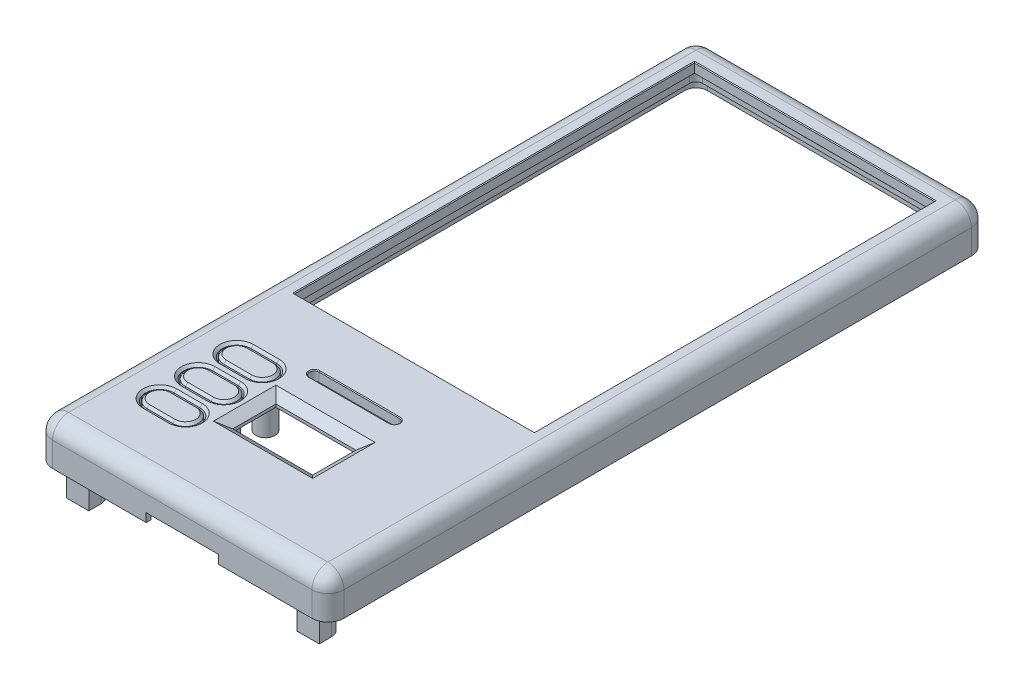
SolidWorks part; units mm, degrees
material "ABS"
ref_plane "Front Plane" through (0, 0, 0) normal (0, 0, 1) x (1, 0, 0)
ref_plane "Top Plane" through (0, 0, 0) normal (0, 1, 0) x (1, 0, 0)
ref_plane "Right Plane" through (0, 0, 0) normal (1, 0, 0) x (0, 0, -1)
sketch "Sketch1" plane through (0, 0, 0) normal (0, 1, 0) x (1, 0, 0)
  line L1 (-45.5, -103) -> (45.5, -103)
  line L2 (-45.5, -103) -> (-45.5, 103)
  line L3 (-45.5, 103) -> (45.5, 103)
  line L4 (45.5, -103) -> (45.5, 103)
  line L5 (-45.5, -103) -> (45.5, 103) construction
  line L6 (-45.5, 103) -> (45.5, -103) construction
  point P0 (0, 0)
  dimension "D1" = 91
  dimension "D2" = 206
extrude "Boss-Extrude1" add sketch "Sketch1" along normal blind 3
fillet "Fillet1" radius 5 4 edges at (45.5, 1.5, -103) (-45.5, 1.5, -103) (-45.5, 1.5, 103) (45.5, 1.5, 103)
sketch "Sketch2" plane through (0, 0, 0) normal (0, -1, 0) x (1, 0, 0)
  line L28 (-40.5, 103) -> (40.5, 103) construction
  line L29 (-40.5, -103) -> (40.5, -103)
  line L30 (-45.5, -98) -> (-45.5, 98)
  line L31 (-40.5, 103) -> (40.5, 103)
  line L32 (45.5, -98) -> (45.5, 98)
  line L33 (-45.5, -103) -> (45.5, 103) construction
  line L34 (-45.5, 103) -> (45.5, -103) construction
  line L35 (45.5, 98) -> (45.5, -98) construction
  line L36 (-42.5, -98) -> (-42.5, 98)
  line L37 (-40.5, 100) -> (40.5, 100)
  line L38 (42.5, -98) -> (42.5, 98)
  line L39 (-40.5, -100) -> (40.5, -100)
  arc A28 (40.5, -103) -> (45.5, -98) centre (40.5, -98) ccw
  arc A29 (-40.5, -103) -> (-45.5, -98) centre (-40.5, -98) cw
  arc A30 (40.5, 103) -> (45.5, 98) centre (40.5, 98) cw
  arc A31 (-45.5, 98) -> (-40.5, 103) centre (-40.5, 98) cw
  arc A32 (-42.5, 98) -> (-40.5, 100) centre (-40.5, 98) cw
  arc A33 (40.5, 100) -> (42.5, 98) centre (40.5, 98) cw
  arc A34 (40.5, -100) -> (42.5, -98) centre (40.5, -98) ccw
  arc A35 (-40.5, -100) -> (-42.5, -98) centre (-40.5, -98) cw
  point P0 (0, 0)
  dimension "D1" = 5
  dimension "D2" = 3
extrude "Boss-Extrude2" add sketch "Sketch2" along normal blind 7
sketch "Sketch3" plane through (0, 0, 0) normal (0, -1, 0) x (1, 0, 0)
  line L0 (40.5, 100) -> (-40.5, 100) construction
  line L1 (-37.5, 30.5) -> (37.5, 30.5)
  line L2 (-37.5, 30.5) -> (-37.5, -94.5)
  line L3 (-37.5, -94.5) -> (37.5, -94.5)
  line L4 (37.5, 30.5) -> (37.5, -94.5)
  line L5 (-37.5, 30.5) -> (37.5, -94.5) construction
  line L6 (-37.5, -94.5) -> (37.5, 30.5) construction
  line L7 (12.5, 49.25) -> (-12.5, 49.25) construction
  line L8 (-12.5, 61.25) -> (12.5, 61.25)
  line L9 (-12.5, 61.25) -> (-12.5, 74.75)
  line L10 (-12.5, 74.75) -> (12.5, 74.75)
  line L11 (12.5, 61.25) -> (12.5, 74.75)
  line L12 (-12.5, 61.25) -> (12.5, 74.75) construction
  line L13 (-12.5, 74.75) -> (12.5, 61.25) construction
  line L14 (12.5, 47.75) -> (-12.5, 47.75)
  line L15 (12.5, 50.75) -> (-12.5, 50.75)
  line L16 (-40.5, -103) -> (40.5, -103) construction
  line L17 (-40.5, 103) -> (40.5, 103) construction
  arc A0 (12.5, 47.75) -> (12.5, 50.75) centre (12.5, 49.25) ccw
  arc A1 (-12.5, 50.75) -> (-12.5, 47.75) centre (-12.5, 49.25) ccw
  point P0 (0, -32)
  point P9 (0, 68)
  point P17 (0, 49.25)
  point P25 (0, 103)
  dimension "D1" = 75
  dimension "D2" = 125
  dimension "D3" = 71
  dimension "D4" = 25
  dimension "D5" = 13.5
  dimension "D6" = 32
  dimension "D7" = 25
  dimension "D8" = 12
  dimension "D9" = 3
extrude "Cut-Extrude1" cut sketch "Sketch3" against normal up to next
sketch "Sketch4" plane through (0, 0, 0) normal (0, -1, 0) x (1, 0, 0)
  line L0 (-21, 80) -> (-21, 56) construction
  line L1 (-12.5, 74.75) -> (-12.5, 61.25) construction
  line L6 (12.5, 74.75) -> (-12.5, 74.75) construction
  circle A0 centre (-21, 80) radius 3
  circle A1 centre (-21, 56) radius 3
  circle A2 centre (-21, 68) radius 3
  point P11 (-12.5, 68)
  point P12 (0, 74.75)
  dimension "D4" = 6
  dimension "D5" = 6
  dimension "D6" = 6
  dimension "D1" = 21
  dimension "D3" = 24
extrude "Boss-Extrude3" add sketch "Sketch4" along normal blind 13
sketch "Sketch5" plane through (0, 0, 0) normal (0, -1, 0) x (1, 0, 0)
  line L2 (-22, 56) -> (-30, 56) construction
  line L3 (-22, 52) -> (-30, 52)
  line L4 (-22, 60) -> (-30, 60)
  line L5 (-21, 59) -> (-21, 53) construction
  line L7 (-22, 51.5) -> (-30, 51.5)
  line L8 (-22, 60.5) -> (-30, 60.5)
  line L9 (-22, 63.5) -> (-30, 63.5)
  line L10 (-22, 72.5) -> (-30, 72.5)
  line L11 (-22, 68) -> (-30, 68) construction
  line L12 (-22, 64) -> (-30, 64)
  line L13 (-22, 72) -> (-30, 72)
  line L14 (-22, 75.5) -> (-30, 75.5)
  line L15 (-22, 84.5) -> (-30, 84.5)
  line L16 (-22, 80) -> (-30, 80) construction
  line L17 (-22, 76) -> (-30, 76)
  line L18 (-22, 84) -> (-30, 84)
  line L19 (-22, 51.5) -> (-22, 63.5) construction
  arc A0 (-22, 52) -> (-22, 60) centre (-22, 56) ccw
  arc A1 (-30, 60) -> (-30, 52) centre (-30, 56) ccw
  circle A11 centre (-21, 56) radius 3 construction
  arc A12 (-30, 60.5) -> (-30, 51.5) centre (-30, 56) ccw
  arc A13 (-22, 51.5) -> (-22, 60.5) centre (-22, 56) ccw
  arc A14 (-30, 72.5) -> (-30, 63.5) centre (-30, 68) ccw
  arc A15 (-22, 63.5) -> (-22, 72.5) centre (-22, 68) ccw
  arc A16 (-22, 64) -> (-22, 72) centre (-22, 68) ccw
  arc A17 (-30, 72) -> (-30, 64) centre (-30, 68) ccw
  arc A18 (-30, 84.5) -> (-30, 75.5) centre (-30, 80) ccw
  arc A19 (-22, 75.5) -> (-22, 84.5) centre (-22, 80) ccw
  arc A20 (-22, 76) -> (-22, 84) centre (-22, 80) ccw
  arc A21 (-30, 84) -> (-30, 76) centre (-30, 80) ccw
  point P2 (-26, 56)
  point P10 (-21, 56)
  point P21 (-26, 68)
  point P34 (-26, 80)
  dimension "D1" = 8
  dimension "D5" = 12
  dimension "D3" = 0.5
  dimension "D4" = 3
  dimension "D2" = 8
extrude "Cut-Extrude4" cut sketch "Sketch5" against normal up to next
sketch "Sketch18" plane through (0, 0, 0) normal (0, -1, 0) x (1, 0, 0)
  line L0 (-33.7081, 66.5) -> (-34.5, 66.5)
  line L1 (-33.7081, 54.5) -> (-34.5, 54.5)
  line L2 (-33.7081, 54.5) -> (-33.7081, 57.5)
  line L3 (-33.7081, 57.5) -> (-34.5, 57.5)
  line L4 (-34.5, 54.5) -> (-34.5, 57.5)
  line L5 (-33.7081, 66.5) -> (-33.7081, 69.5)
  line L6 (-33.7081, 69.5) -> (-34.5, 69.5)
  line L7 (-34.5, 66.5) -> (-34.5, 69.5)
  line L8 (-33.7081, 78.5) -> (-34.5, 78.5)
  line L9 (-33.7081, 78.5) -> (-33.7081, 81.5)
  line L10 (-33.7081, 81.5) -> (-34.5, 81.5)
  line L11 (-34.5, 78.5) -> (-34.5, 81.5)
  line L12 (-33.7081, 54.5) -> (-33.7081, 66.5) construction
  arc A0 (-30, 60) -> (-30, 52) centre (-30, 56) ccw construction
  arc A1 (-30, 60.5) -> (-30, 51.5) centre (-30, 56) ccw construction
  point P13 (-34, 56)
  point P14 (-33.7081, 56)
  dimension "D1" = 3
  dimension "D3" = 12
  dimension "D2" = 3
extrude "Boss-Extrude8" add sketch "Sketch18" against normal blind 2
sketch "Sketch8" plane through (0, -7, 0) normal (0, -1, 0) x (1, 0, 0)
  line L12 (40.5, 103) -> (-40.5, 103) construction
  line L13 (45.5, -98) -> (45.5, 98) construction
  line L14 (-45.5, 98) -> (-45.5, -98) construction
  line L15 (-40.5, -103) -> (40.5, -103) construction
  line L16 (40.5, 103) -> (-40.5, 103)
  line L17 (45.5, -98) -> (45.5, 98)
  line L18 (-45.5, 98) -> (-45.5, -98)
  line L19 (-40.5, -103) -> (40.5, -103)
  line L20 (40.5, 101.5) -> (-40.5, 101.5)
  line L21 (-44, 98) -> (-44, -98)
  line L22 (-40.5, -101.5) -> (40.5, -101.5)
  line L23 (44, -98) -> (44, 98)
  arc A12 (45.5, 98) -> (40.5, 103) centre (40.5, 98) ccw construction
  arc A13 (-40.5, 103) -> (-45.5, 98) centre (-40.5, 98) ccw construction
  arc A14 (40.5, -103) -> (45.5, -98) centre (40.5, -98) ccw construction
  arc A15 (-45.5, -98) -> (-40.5, -103) centre (-40.5, -98) ccw construction
  arc A16 (45.5, 98) -> (40.5, 103) centre (40.5, 98) ccw
  arc A17 (-40.5, 103) -> (-45.5, 98) centre (-40.5, 98) ccw
  arc A18 (40.5, -103) -> (45.5, -98) centre (40.5, -98) ccw
  arc A19 (-45.5, -98) -> (-40.5, -103) centre (-40.5, -98) ccw
  arc A20 (-40.5, 101.5) -> (-44, 98) centre (-40.5, 98) ccw
  arc A21 (-44, -98) -> (-40.5, -101.5) centre (-40.5, -98) ccw
  arc A22 (40.5, -101.5) -> (44, -98) centre (40.5, -98) ccw
  arc A23 (44, 98) -> (40.5, 101.5) centre (40.5, 98) ccw
  dimension "D1" = 1.5
extrude "Boss-Extrude4" add sketch "Sketch8" along normal blind 2.7
fillet "Fillet2" radius 5 8 edges at (44.0355, 3, 101.5355) (0, 3, 103) (-44.0355, 3, 101.5355) (-45.5, 3, 0) (-44.0355, 3, -101.5355) (0, 3, -103) (44.0355, 3, -101.5355) (45.5, 3, 0)
sketch "Sketch9" plane through (0, 0, 103) normal (0, 0, 1) x (1, 0, 0)
  line L1 (-11.25, -7) -> (11.25, -7)
  line L2 (-11.25, -7) -> (-11.25, -9.7)
  line L3 (-11.25, -9.7) -> (11.25, -9.7)
  line L4 (11.25, -7) -> (11.25, -9.7)
  line L5 (-11.25, -7) -> (11.25, -9.7) construction
  line L6 (-11.25, -9.7) -> (11.25, -7) construction
  line L7 (40.5, -7) -> (-40.5, -7) construction
  line L8 (40.5, -9.7) -> (-40.5, -9.7) construction
  point P0 (0, -8.35)
  dimension "D1" = 22.5
extrude "Cut-Extrude6" cut sketch "Sketch9" against normal up to next
sketch "Sketch12" plane through (0, 0, 0) normal (0, -1, 0) x (1, 0, 0)
  line L0 (-39.5, 95.9) -> (-39.5, 100)
  line L2 (-39.5, 100) -> (-32.5, 100)
  line L3 (40.5, 100) -> (-40.5, 100) construction
  line L4 (-32.5, 100) -> (-32.5, 95.9)
  line L5 (32.5, 95.9) -> (32.5, 100)
  line L7 (32.5, 100) -> (39.5, 100)
  line L8 (39.5, 100) -> (39.5, 95.9)
  line L9 (11.25, 103) -> (-11.25, 103) construction
  arc A0 (32.5, 95.9) -> (39.5, 95.9) centre (36, 95.9) ccw
  circle A1 centre (36, 95.9) radius 1.4
  circle A2 centre (-36, 95.9) radius 1.4
  arc A3 (-39.5, 95.9) -> (-32.5, 95.9) centre (-36, 95.9) ccw
  point P20 (0, 103)
  dimension "D1" = 7
  dimension "D2" = 7
  dimension "D3" = 2.8
  dimension "D4" = 2.8
  dimension "D5" = 4.1
  dimension "D6" = 36
  dimension "D7" = 36
  dimension "D8" = 4.1
extrude "Boss-Extrude7" add sketch "Sketch12" along normal blind 18.8
sketch "Sketch13" plane through (0, 0, 0) normal (0, -1, 0) x (1, 0, 0)
  line L0 (37.5, 30.5) -> (-37.5, 30.5) construction
  line L6 (-15, 30.5) -> (15, 30.5)
  line L7 (-15, 30.5) -> (-15, 40.5)
  line L8 (-15, 40.5) -> (15, 40.5)
  line L9 (15, 30.5) -> (15, 40.5)
  point P6 (0, 30.5)
  point P7 (0, 30.5)
  dimension "D1" = 30
  dimension "D2" = 10
extrude "Cut-Extrude7" cut sketch "Sketch13" against normal blind 1
sketch "Sketch14" plane through (0, 0, 0) normal (0, -1, 0) x (1, 0, 0)
  line L0 (12.5, 74.75) -> (-12.5, 74.75) construction
  line L1 (-13, 82) -> (13, 82)
  line L2 (-13, 82) -> (-13, 88)
  line L3 (-13, 88) -> (13, 88)
  line L4 (13, 82) -> (13, 88)
  line L5 (-13, 82) -> (13, 88) construction
  line L6 (-13, 88) -> (13, 82) construction
  line L7 (32.5, 100) -> (-32.5, 100) construction
  point P0 (0, 85)
  point P8 (0, 74.75)
  dimension "D1" = 6
  dimension "D2" = 26
  dimension "D3" = 15
extrude "Cut-Extrude8" cut sketch "Sketch14" against normal blind 2
sketch "Sketch16" plane through (0, 0, 100) normal (0, 0, 1) x (1, 0, 0)
  line L1 (-39.5, -7) -> (-32.5, -7)
  line L2 (-39.5, -7) -> (-39.5, -18.8)
  line L3 (-39.5, -18.8) -> (-32.5, -18.8)
  line L4 (-32.5, -7) -> (-32.5, -18.8)
  line L5 (39.5, -7) -> (32.5, -7)
  line L6 (39.5, -7) -> (39.5, -18.8)
  line L7 (39.5, -18.8) -> (32.5, -18.8)
  line L8 (32.5, -7) -> (32.5, -18.8)
extrude "Cut-Extrude10" cut sketch "Sketch16" against normal blind 0.3
sketch "Sketch17" plane through (0, 0, -100) normal (0, 0, 1) x (1, 0, 0)
  line L1 (-19.51, -5.55) -> (19.51, -5.55)
  line L2 (-21, -4.06) -> (-21, -3.94)
  line L3 (-19.51, -2.45) -> (19.51, -2.45)
  line L4 (21, -4.06) -> (21, -3.94)
  line L5 (-21, -5.55) -> (21, -2.45) construction
  line L6 (-21, -2.45) -> (21, -5.55) construction
  line L7 (-40.5, -7) -> (40.5, -7) construction
  arc A0 (19.51, -5.55) -> (21, -4.06) centre (19.51, -4.06) ccw
  arc A1 (19.51, -2.45) -> (21, -3.94) centre (19.51, -3.94) cw
  arc A2 (-19.51, -5.55) -> (-21, -4.06) centre (-19.51, -4.06) cw
  arc A3 (-21, -3.94) -> (-19.51, -2.45) centre (-19.51, -3.94) cw
  point P0 (0, -4)
  dimension "D4" = 1.49
  dimension "D1" = 3.1
  dimension "D2" = 42
  dimension "D3" = 3
extrude "Cut-Extrude11" cut sketch "Sketch17" against normal blind 1.6
fillet "Fillet11" radius 1.5 8 edges at (-21, -4, -101.6) (-20.5636, -2.8864, -101.6) (0, -2.45, -101.6) (20.5636, -2.8864, -101.6) (21, -4, -101.6) (20.5636, -5.1136, -101.6) (0, -5.55, -101.6) (-20.5636, -5.1136, -101.6)
chamfer "Chamfer1" distance 3 angle 35 4 edges at (-12.5, 3, 68) (0, 3, 61.25) (12.5, 3, 68) (0, 3, 74.75) first distance on face at (0, 3, 0)
chamfer "Chamfer2" distance 0.75 angle 45 24 edges at (-34, 3, 56) (-26, 3, 60) (-26, 3, 52) (-18, 3, 56) (-34.5, 3, 56) (-26, 3, 60.5) (-26, 3, 51.5) (-17.5, 3, 56) (-34, 3, 68) (-26, 3, 72) (-26, 3, 64) (-18, 3, 68) (-34.5, 3, 68) (-26, 3, 72.5) (-26, 3, 63.5) (-17.5, 3, 68) (-34, 3, 80) (-26, 3, 84) (-26, 3, 76) (-18, 3, 80) (-34.5, 3, 80) (-26, 3, 84.5) (-26, 3, 75.5) (-17.5, 3, 80)
chamfer "Chamfer3" distance 0.25 angle 45 8 edges at (0, 3, 47.75) (-14, 3, 49.25) (14, 3, 49.25) (0, 3, 50.75) (0, 3, -94.5) (37.5, 3, -32) (-37.5, 3, -32) (0, 3, 30.5)
